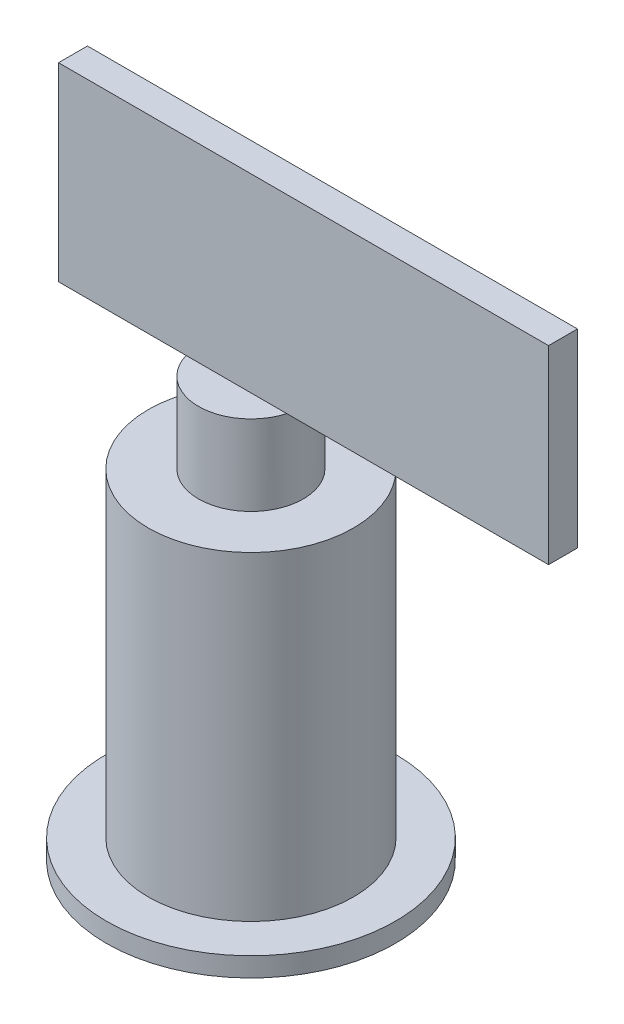
SolidWorks part; units mm, degrees
ref_plane "Front Plane" through (0, 0, 0) normal (0, 0, 1) x (1, 0, 0)
ref_plane "Top Plane" through (0, 0, 0) normal (0, 1, 0) x (1, 0, 0)
ref_plane "Right Plane" through (0, 0, 0) normal (1, 0, 0) x (0, 0, -1)
sketch "Sketch2" plane through (0, 0, 0) normal (0, 1, 0) x (1, 0, 0)
  circle A0 centre (0, 0) radius 5.435
  dimension "D1" = 10.87
extrude "Boss-Extrude1" add sketch "Sketch2" along normal blind 8.32
sketch "Sketch4" plane through (0, 0, 0) normal (0, 0, 1) x (1, 0, 0)
  line L0 (0, 8.32) -> (0, 28.01) construction
  line L1 (5.435, 8.32) -> (-5.435, 8.32) construction
  line L2 (-5.435, 8.32) -> (-5.435, 28.01) construction
  line L3 (-18.465, 28.01) -> (32.385, 28.01)
  line L4 (-18.465, 28.01) -> (-18.465, 8.32)
  line L5 (-18.465, 8.32) -> (32.385, 8.32)
  line L6 (32.385, 28.01) -> (32.385, 8.32)
  line L7 (-5.435, 8.32) -> (-5.435, 0) construction
  point P11 (0, 0)
  point P12 (0, 0)
  point P15 (0, 0)
  point P18 (0, 0)
  dimension "D1" = 19.69
  dimension "D2" = 37.82
  dimension "D3" = 50.85
extrude "Boss-Extrude2" add sketch "Sketch4" along normal blind 1.5 and the other way blind 1.5
sketch "Sketch5" plane through (0, 0, 0) normal (0, -1, 0) x (1, 0, 0)
  circle A0 centre (0, 0) radius 10.65
  dimension "D1" = 21.3
extrude "Boss-Extrude3" add sketch "Sketch5" along normal blind 33.16
sketch "Sketch6" plane through (0, -33.16, 0) normal (0, -1, 0) x (1, 0, 0)
  circle A0 centre (0, 0) radius 15
  dimension "D1" = 30
extrude "Boss-Extrude4" add sketch "Sketch6" along normal blind 2
